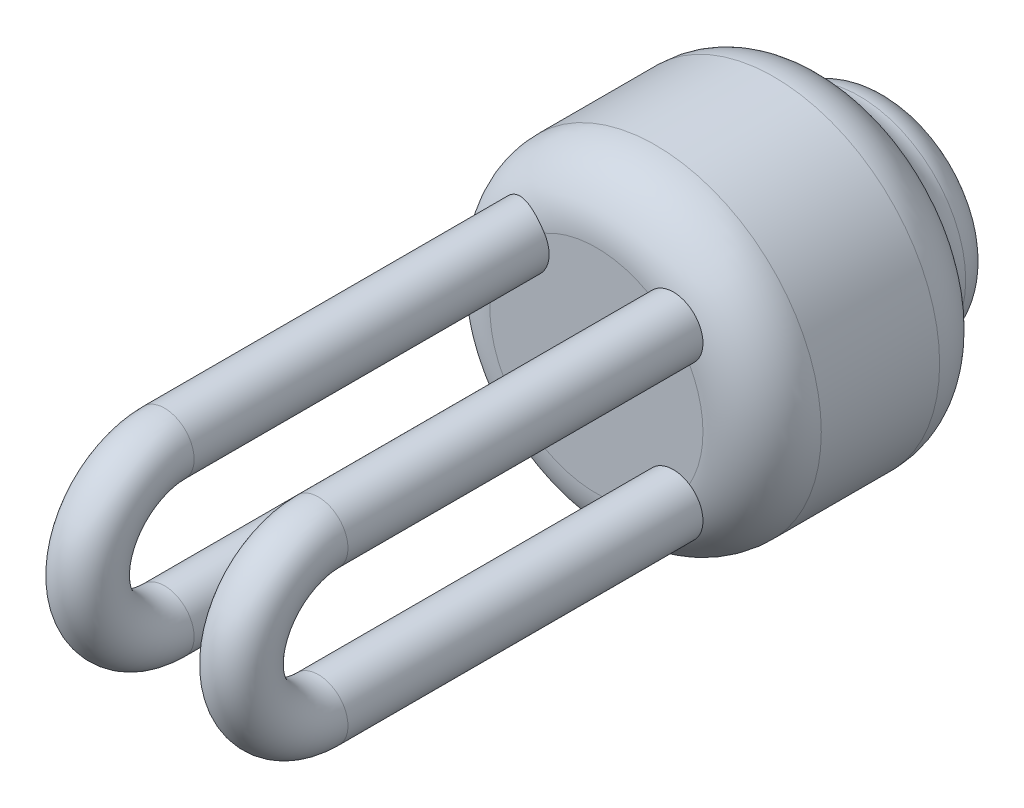
SolidWorks part; units mm, degrees
ref_plane "前视基准面" through (0, 0, 0) normal (0, 0, 1) x (1, 0, 0)
ref_plane "上视基准面" through (0, 0, 0) normal (0, 1, 0) x (1, 0, 0)
ref_plane "右视基准面" through (0, 0, 0) normal (1, 0, 0) x (0, 0, -1)
sketch "草图1" plane through (0, 0, 0) normal (0, 0, 1) x (1, 0, 0)
  circle A0 centre (0, 0) radius 28
  dimension "D1" = 56
extrude "凸台-拉伸1" add sketch "草图1" along normal blind 40
sketch "草图2" plane through (0, 0, 40) normal (0, 0, 1) x (1, 0, 0)
  circle A0 centre (-13, 13) radius 5
  point P5 (-40.9071, 4.6809)
  point P8 (-16.892, -3.0528)
  dimension "D1" = 13
  dimension "D3" = 10
  dimension "D2" = 13
ref_plane "基准面1" through (-13, 0, 0) normal (1, 0, 0) x (0, 0, -1)
sketch "草图3" plane through (-13, 0, 0) normal (1, 0, 0) x (0, 0, -1)
  line L0 (-40, 13) -> (-100, 13)
  line L1 (-40, 18) -> (-40, 8) construction
  line L2 (-56.9385, 0) -> (24.4382, 0) construction
  line L3 (-40, -13) -> (-100, -13)
  arc A0 (-100, 13) -> (-100, -13) centre (-100, 0) ccw
  dimension "D1" = 60
sweep "扫描1" add profiles "草图2" path "草图3"
fillet "圆角1" radius 10 2 edges at (28, 0, 0) (28, 0, 40)
mirror "镜向1" about plane through (0, 0, 0) normal (1, 0, 0) of "扫描1"
sketch "草图4" plane through (0, 0, 0) normal (0, 0, -1) x (-1, 0, 0)
  circle A0 centre (0, 0) radius 18
  dimension "D1" = 36
extrude "凸台-拉伸2" add sketch "草图4" along normal blind 10
fillet "圆角2" radius 6 1 edges at (-18, 0, -10)
fillet "圆角3" radius 6 1 edges at (18, 0, 0)
